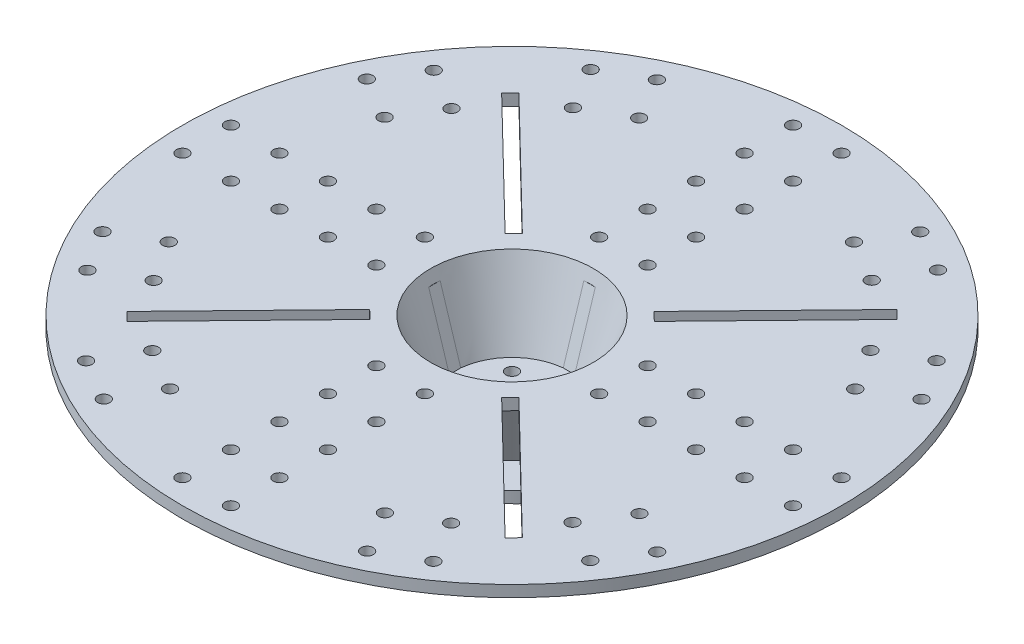
SolidWorks part; units mm, degrees
note: '?' marks a value the reader was unsure of.
material "ULTEM 9085"
ref_plane "Front Plane" through (0, 0, 0) normal (0, 0, 1) x (1, 0, 0)
ref_plane "Top Plane" through (0, 0, 0) normal (0, 1, 0) x (1, 0, 0)
ref_plane "Right Plane" through (0, 0, 0) normal (1, 0, 0) x (0, 0, -1)
other "Center of Mass"
sketch "Sketch1" plane through (0, 0, 0) normal (0, 0, 1) x (1, 0, 0)
  line L0 (0, -40.25) -> (0, -46.25)
  line L1 (0, -40.25) -> (30, -40.25)
  line L2 (30, -40.25) -> (42.6498, 0)
  line L3 (42.6498, 0) -> (172.6498, 0)
  line L4 (188.8148, 0) -> (-188.8148, 0) construction
  line L5 (172.6498, 0) -> (172.6498, -6)
  line L6 (42.6498, 0) -> (42.6498, -31.4331) construction
  line L7 (172.6498, -6) -> (46.8968, -6)
  line L8 (36.1179, -40.2971) -> (46.8968, -6)
  line L9 (36.1179, -40.2971) -> (55.5, -40.2971)
  line L10 (55.5, -40.2971) -> (55.5, -46.25)
  line L11 (55.5, -46.25) -> (0, -46.25)
  line L12 (0, -25.4375) -> (0, 25.4375) construction
  point P15 (0, -43.25)
  point P16 (55.5, -43.2736)
  point P24 (36.3249, -20.125)
  point P25 (41.5074, -23.1486)
  dimension "D1" = 72.553
  dimension "D2" = 30
  dimension "D3" = 130
  dimension "D4" = 6
  dimension "D5" = 6
  dimension "D6" = 55.5
  dimension "D7" = 34.2971
  dimension "D8" = 40.25
  dimension "D9" = 6
revolve "Revolve2" add sketch "Sketch1" angle 360 about L0
ref_axis "Axis1" through (0, 0, 0) along (0, -1, 0)?
sketch "Sketch3" plane through (0, 0, 0) normal (0, 0, 1) x (1, 0, 0)
  line L0 (55.5, -40.2971) -> (172.6498, -6)
  line L1 (172.6498, -6) -> (0, -6)
  line L2 (-172.6498, -6) -> (172.6498, -6) construction
  line L3 (0, -6) -> (0, -40.2971)
  line L4 (55.5, -40.2971) -> (-55.5, -40.2971) construction
  line L5 (0, -40.2971) -> (55.5, -40.2971)
extrude "Boss-Extrude2" add sketch "Sketch3" along normal mid plane 6
pattern_circular "CirPattern2" count 4 over 360 about axis through (0, 0, 0) along (0, 1, 0) of "Boss-Extrude2"
sketch "Sketch6" plane through (0, 0, 3) normal (0, 0, 1) x (1, 0, 0)
  line L0 (-3, -6) -> (-40.6536, -6)
  line L1 (-40.6536, -6) -> (-29.8496, -40.25)
  line L2 (-29.8496, -40.25) -> (-3, -40.25)
  line L3 (-3, -40.25) -> (-3, -6)
  spline S0 degree 3 poles (-29.8496, -40.25) (-33.4553, -28.8347) (-37.0555, -17.4177) (-40.6536, -6) knots 0 0 0 0 1 1 1 1 construction
extrude "Cut-Extrude3" cut sketch "Sketch6" against normal blind 6
pattern_circular "CirPattern4" count 4 over 360 about axis through (0, 0, 0) along (0, 1, 0) of "Cut-Extrude3"
sketch "Sketch7" plane through (0, -6, 0) normal (0, 1, 0) x (1, 0, 0)
  line L0 (-3, 3) -> (-3, -3)
  line L1 (-3, -3) -> (3, -3)
  line L2 (-3, -3) -> (3, -3) construction
  line L3 (3, -3) -> (3, 3)
  line L4 (3, 3) -> (-3, 3) construction
  line L5 (3, 3) -> (-3, 3)
extrude "Cut-Extrude4" cut sketch "Sketch7" against normal up to surface (34.25 mm away) up to face at (0, -40.25, 0)
sketch "Sketch8" plane through (0, -40.25, 0) normal (0, 1, 0) x (1, 0, 0)
  circle A0 centre (0, 0) radius 3.175
  dimension "D1" = 6.35
extrude "Cut-Extrude5" cut sketch "Sketch8" against normal through all
sketch "Sketch11" plane through (0, -6, 0) normal (0, -1, 0) x (1, 0, 0)
  line L0 (0, -25.4375) -> (0, 25.4375) construction
  circle A0 centre (-12.7, 159.9498) radius 3.2
  arc A2 (3, 172.6237) -> (0, 172.6498) centre (0, 0) ccw construction
  point P9 (0, 172.6498)
  dimension "D1" = 6.4
  dimension "D2" = 12.7
  dimension "D3" = 12.7
extrude "Cut-Extrude6" cut sketch "Sketch11" against normal through all
pattern_linear "LPattern2" count 2 spacing 25.4 along (1, 0, 0) count 5 spacing 25.4 along (0, 0, -1) of "Cut-Extrude6"
pattern_circular "CirPattern5" count 4 over 360 about axis through (0, 0, 0) along (0, 1, 0) of "LPattern2", "Cut-Extrude6"
sketch "Sketch12" plane through (0, 0, 0) normal (0, 1, 0) x (1, 0, 0)
  line L0 (0, 0) -> (-149.5191, -86.3249) construction
  line L1 (-25.4375, 0) -> (25.4375, 0) construction
  circle A0 centre (0, 0) radius 172.6498 construction
  dimension "D1" = 30
sketch "Sketch13" plane through (0, 0, 0) normal (0, 1, 0) x (1, 0, 0)
  line L0 (0, 0) -> (149.5191, -86.3249) construction
  line L1 (-25.4375, 0) -> (25.4375, 0) construction
  circle A0 centre (0, 0) radius 172.6498 construction
  dimension "D1" = 30
sketch "Sketch15" plane through (0, 0, 0) normal (0, 1, 0) x (1, 0, 0)
  line L0 (149.5191, -86.3249) -> (115.5001, -140.2476) construction
sketch "Sketch17" plane through (0, 0, 0) normal (0, 1, 0) x (1, 0, 0)
  line L0 (0, 0) -> (149.5191, -86.3249) construction
  line L1 (149.5191, -86.3249) -> (115.5001, -140.2476) construction
  circle A0 centre (131.7305, -90.7194) radius 3.2
  dimension "D1" = 6.4
  dimension "D2" = 12.7
  dimension "D3" = 12.7
extrude "Cut-Extrude7" cut sketch "Sketch17" against normal through all
pattern_linear "LPattern3" count 2 spacing 25.4 along (-0.866, 0, -0.5) count 2 spacing 25.4 along (0.5336, 0, -0.8458) of "Cut-Extrude7"
mirror "Mirror1" about plane through (0, 0, 0) normal (1, 0, 0) of "LPattern3", "Cut-Extrude7"
mirror "Mirror2" about plane through (0, 0, 0) normal (0, 0, 1) of "Mirror1", "Cut-Extrude7", "LPattern3"
sketch "Sketch18" plane through (0, 0, 0) normal (0, 1, 0) x (1, 0, 0)
  line L0 (0, 0) -> (122.0818, 122.0818) construction
  line L1 (-25.4375, 0) -> (25.4375, 0) construction
  circle A0 centre (0, 0) radius 172.6498 construction
  dimension "D1" = 45
sketch "Sketch19" plane through (0, 0, 0) normal (0, 1, 0) x (1, 0, 0)
  line L0 (102.7184, 99.0924) -> (98.1294, 103.5535)
  line L1 (102.7184, 99.0924) -> (39.9847, 34.5596)
  line L2 (98.1294, 103.5535) -> (35.3957, 39.0207)
  line L3 (39.9847, 34.5596) -> (35.3957, 39.0207)
  line L4 (0, 0) -> (122.0818, 122.0818) construction
  point P6 (100.4239, 101.323)
  point P8 (71.3515, 66.826)
  dimension "D1" = 3.2
  dimension "D2" = 6.4
  dimension "D3" = 90
  dimension "D4" = 30
extrude "Cut-Extrude8" cut sketch "Sketch19" against normal up to next
pattern_circular "CirPattern6" count 4 over 360 about axis through (0, 0, 0) along (0, 1, 0) of "Cut-Extrude8"
sketch "Sketch23" plane through (0, -46.25, 0) normal (0, -1, 0) x (1, 0, 0)
  line L0 (23, -39.8372) -> (0, 0) construction
  line L1 (0, -25.4375) -> (0, 25.4375) construction
  circle A0 centre (23, -39.8372) radius 3.2
  dimension "D1" = 6.4
  dimension "D3" = 30
  dimension "D2" = 46
extrude "Cut-Extrude9" cut sketch "Sketch23" along direction (0, 1, 0) on the side against the normal up to next (5.9529 mm away)
pattern_circular "CirPattern7" count 2 every 30 about axis through (0, 0, 0) along (0, -1, 0) of "Cut-Extrude9"
pattern_circular "CirPattern8" count 4 over 360 about axis through (0, 0, 0) along (0, 1, 0) of "CirPattern7", "Cut-Extrude9"
sketch "Sketch24" plane through (0, 0, 0) normal (0, 1, 0) x (1, 0, 0)
  line L0 (86.3249, -149.5191) -> (0, 0) construction
  line L1 (0, -25.4375) -> (0, 25.4375) construction
  circle A0 centre (0, 0) radius 172.6498 construction
  dimension "D1" = 30
sketch "Sketch25" plane through (0, 0, 0) normal (0, 1, 0) x (1, 0, 0)
  line L0 (86.3249, -149.5191) -> (54.8663, -167.6817) construction
  line L1 (86.3249, -149.5191) -> (0, 0) construction
  dimension "D1" = 90
sketch "Sketch26" plane through (0, 0, 0) normal (0, 1, 0) x (1, 0, 0)
  line L0 (86.3249, -149.5191) -> (54.8663, -167.6817) construction
  line L1 (86.3249, -149.5191) -> (0, 0) construction
  circle A0 centre (68.9764, -144.8706) radius 3.2
  dimension "D1" = 6.4
  dimension "D2" = 12.7
  dimension "D3" = 12.7
extrude "Cut-Extrude10" cut sketch "Sketch26" against normal through all
pattern_linear "LPattern4" count 2 spacing 25.4 along (-0.5, 0, -0.866) count 2 spacing 25.4 along (0.866, 0, -0.5) of "Cut-Extrude10"
mirror "Mirror3" about plane through (0, 0, 0) normal (1, 0, 0) of "LPattern4", "Cut-Extrude10"
mirror "Mirror4" about plane through (0, 0, 0) normal (0, 0, 1) of "Mirror3", "Cut-Extrude10", "LPattern4"
sketch "Sketch27" plane through (0, -46.25, 0) normal (0, -1, 0) x (1, 0, 0)
  line L0 (0, 0) -> (122.0818, -122.0818) construction
  circle A0 centre (14.8492, -14.8492) radius 3.2
  dimension "D1" = 6.4
  dimension "D2" = 21
extrude "Cut-Extrude11" cut sketch "Sketch27" against normal up to next
pattern_circular "CirPattern9" count 4 over 360 about axis through (0, 0, 0) along (0, 1, 0) of "Cut-Extrude11"
sketch "Sketch28" plane through (3, 0, 0) normal (1, 0, 0) x (0, 0, -1)
  line L0 (0, 25.4375) -> (0, -25.4375) construction
  line L1 (51, -12.4) -> (107, -12.4)
  line L2 (51, -12.4) -> (51, -18.8)
  line L3 (51, -18.8) -> (107, -18.8)
  line L4 (107, -12.4) -> (107, -18.8)
  line L5 (3, -6) -> (172.6237, -6) construction
  dimension "D1" = 6.4
  dimension "D2" = 51
  dimension "D3" = 6.4
  dimension "D4" = 56
extrude "Cut-Extrude12" cut sketch "Sketch28" against normal up to next
pattern_circular "CirPattern10" count 4 over 360 about axis through (0, 0, 0) along (0, 1, 0) of "Cut-Extrude12"
